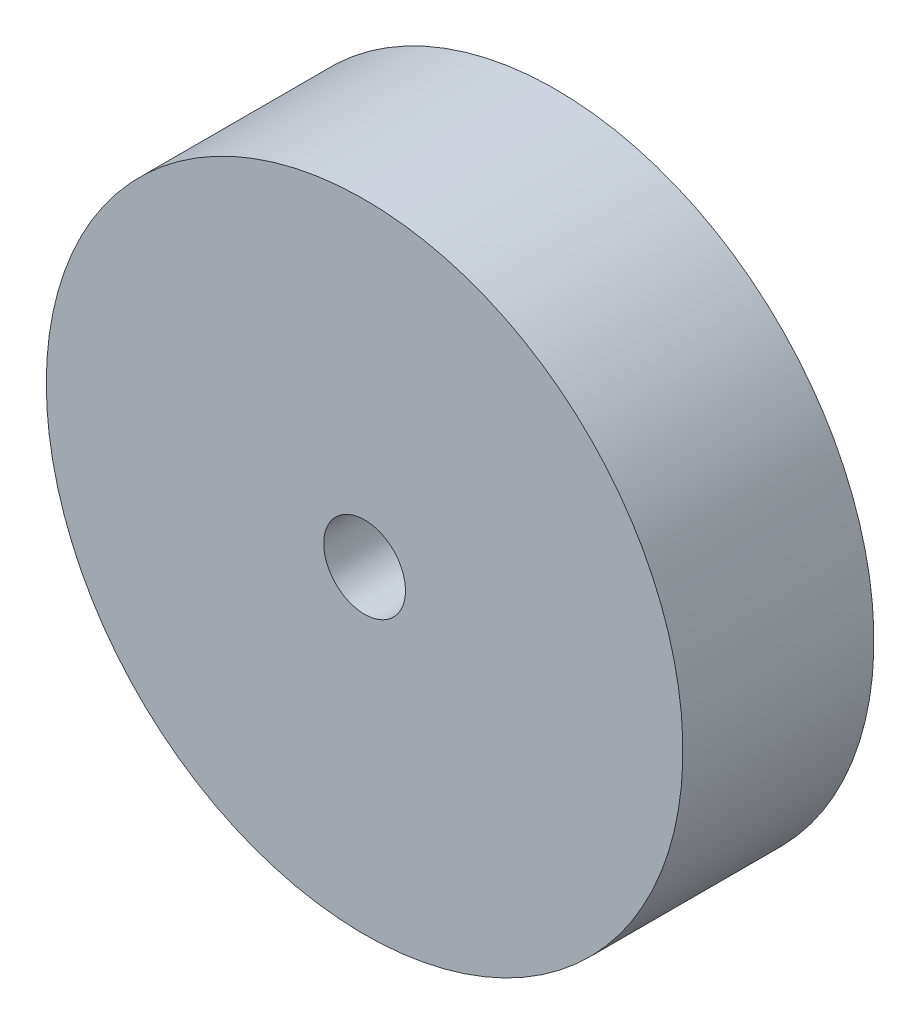
SolidWorks part; units mm, degrees
material "6061-T6 (SS)"
ref_plane "Front Plane" through (0, 0, 0) normal (0, 0, 1) x (1, 0, 0)
ref_plane "Top Plane" through (0, 0, 0) normal (0, 1, 0) x (1, 0, 0)
ref_plane "Right Plane" through (0, 0, 0) normal (1, 0, 0) x (0, 0, -1)
sketch "Sketch1" plane through (0, 0, 0) normal (0, 0, 1) x (1, 0, 0)
  circle A0 centre (0, 0) radius 12.7
  dimension "D1" = 25.4
extrude "Boss-Extrude1" add sketch "Sketch1" along normal blind 7.62
hole_wizard "#4 Clearance Hole1" positions "Sketch2" profile "Sketch3" hole size "#4" standard "ANSI Inch" end condition through all
sketch "Sketch2" plane through (0, 0, 7.62) normal (0, 0, 1) x (1, 0, 0)
  point P0 (0, 0)
sketch "Sketch3" plane through (0, 0, 7.62) normal (1, 0, 0) x (0, -1, 0)
  line L0 (0, 0) -> (0, 7.62)
  line L1 (0, 7.62) -> (1.6319, 7.62)
  line L2 (1.6319, 7.62) -> (1.6319, 0)
  line L5 (1.6319, 0) -> (0, 0)
  line L11 (0, -6.35) -> (0, 107.95) construction
  dimension "Thru Hole Dia." = 3.2639
  dimension "Thru Hole Depth" = 7.62
